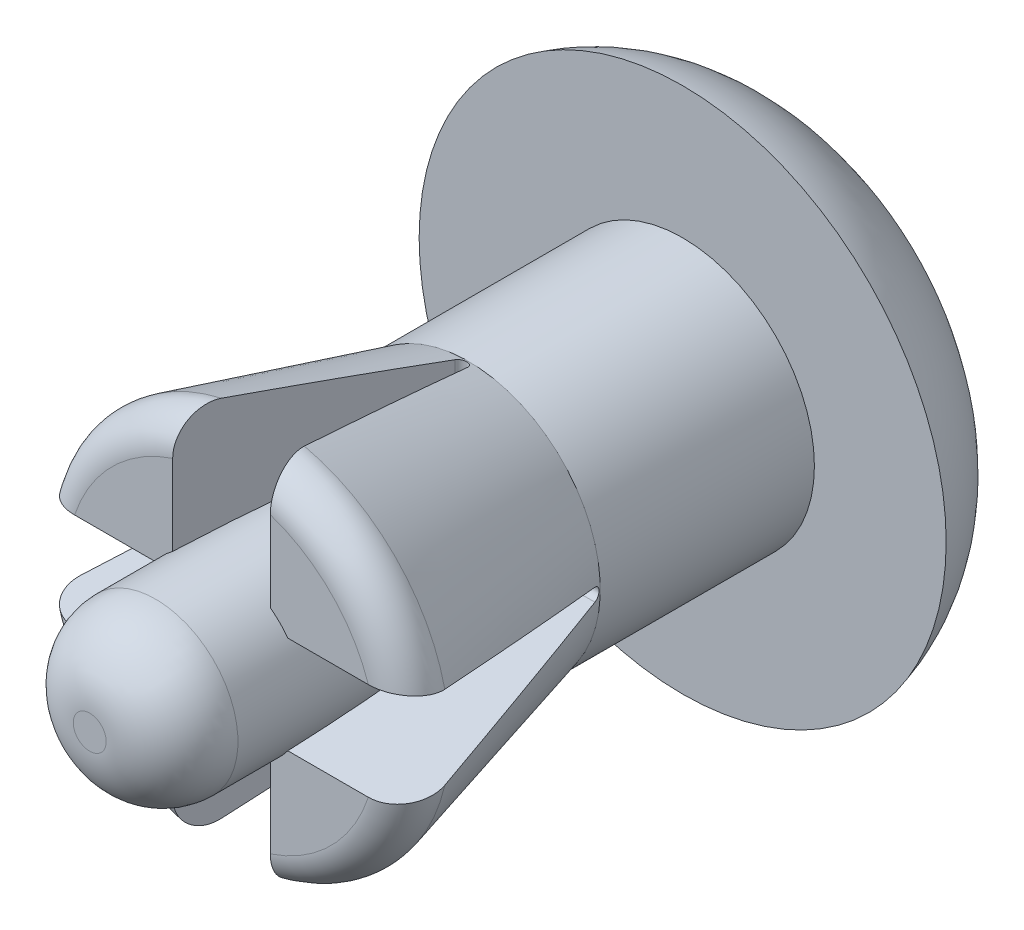
SolidWorks part; units mm, degrees
material "PE Low/Medium Density"
ref_plane "Front Plane" through (0, 0, 0) normal (0, 0, 1) x (1, 0, 0)
ref_plane "Top Plane" through (0, 0, 0) normal (0, 1, 0) x (1, 0, 0)
ref_plane "Right Plane" through (0, 0, 0) normal (1, 0, 0) x (0, 0, -1)
sketch "Sketch1" plane through (0, 0, 0) normal (0, 1, 0) x (1, 0, 0)
  line L0 (0, -9) -> (0, 2)
  line L1 (0, 5.0635) -> (0, -10.819) construction
  line L2 (2, 0) -> (4, 0)
  line L3 (2, 0) -> (2, -3.25)
  line L4 (2, -3.25) -> (3, -7)
  line L5 (3, -7) -> (1.25, -7)
  line L6 (1.25, -7) -> (1.25, -9)
  line L7 (1.25, -9) -> (0, -9)
  arc A0 (0, 2) -> (1.9975, 1.8326) centre (0, -10) cw
  arc A1 (1.9975, 1.8326) -> (4, 0) centre (1.5813, -0.6325) cw
  dimension "D5" = 12
  dimension "D6" = 2.5
  dimension "D1" = 2
  dimension "D2" = 11
  dimension "D3" = 8
  dimension "D4" = 4
  dimension "D7" = 9
  dimension "D8" = 3.25
  dimension "D9" = 6
  dimension "D10" = 2.5
revolve "Revolve1" add sketch "Sketch1" angle 360 about L1
fillet "Fillet1" radius 1 1 edges at (-1.25, 0, 9)
fillet "Fillet2" radius 0.5 1 edges at (-3, 0, 7)
ref_plane "Plane1" through (0, 4, 0) normal (0, 1, 0) x (1, 0, 0)
sketch "Sketch2" plane through (0, 4, 0) normal (0, 1, 0) x (1, 0, 0)
  line L0 (0, 4.7066) -> (0, -12.7867) construction
  line L1 (0, -2.8) -> (0.7406, -7)
  line L2 (0.7406, -7) -> (-0.7406, -7)
  line L3 (0, -2.8) -> (-0.7406, -7)
  line L4 (-2.3492, -7) -> (2.3492, -7) construction
  line L5 (-2, 0) -> (2, 0) construction
  point P7 (0, -7)
  dimension "D1" = 20
  dimension "D2" = 2.8
extrude "Cut-Extrude1" cut sketch "Sketch2" against normal up to surface (2.993 mm away) up to face at (-1.25, 0, 8)
fillet "Fillet3" radius 0.1 1 edges at (0, 1.625, 2.8)
pattern_circular "CirPattern1" count 4 over 360 of "Cut-Extrude1", "Fillet3"
